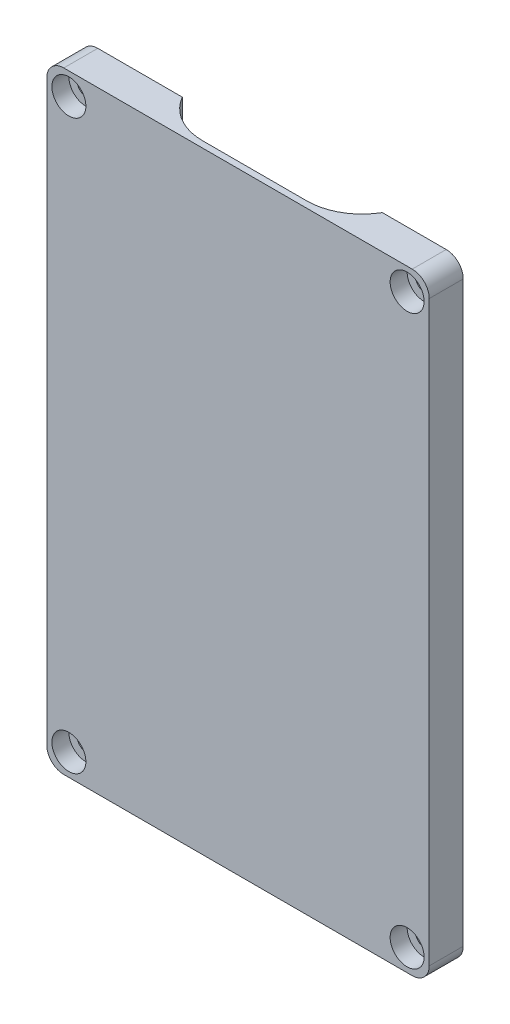
SolidWorks part; units mm, degrees
other "标注1"
sketch "草图6" plane through (-121.7901, 77.7286, -9) normal (-0.0529, 0.1135, -0.9921) x (-0.9984, 0.0112, 0.0545)
ref_plane "前视基准面" through (0, 0, 0) normal (0, 0, 1) x (1, 0, 0)
ref_plane "上视基准面" through (0, 0, 0) normal (0, 1, 0) x (1, 0, 0)
ref_plane "右视基准面" through (0, 0, 0) normal (1, 0, 0) x (0, 0, -1)
sketch "草图1" plane through (0, 0, 0) normal (0, 0, 1) x (1, 0, 0)
  line L1 (-97.7901, 77.7286) -> (-120.2901, 77.7286)
  line L2 (-97.7901, 77.7286) -> (-97.7901, 41.7286)
  line L3 (-97.7901, 41.7286) -> (-120.2901, 41.7286)
  line L4 (-120.2901, 77.7286) -> (-120.2901, 41.7286)
  dimension "D1" = 22.5
  dimension "D2" = 36
extrude "凸台-拉伸1" add sketch "草图1" along normal blind 2
sketch "草图9" plane through (0, 0, 2) normal (0, 0, 1) x (1, 0, 0)
  line L1 (-97.7901, 41.7286) -> (-97.7901, 77.7286) construction
  line L5 (-120.2901, 41.7286) -> (-97.7901, 41.7286) construction
  line L6 (-120.2901, 77.7286) -> (-120.2901, 41.7286) construction
  line L7 (-97.7901, 77.7286) -> (-120.2901, 77.7286) construction
  circle A0 centre (-99.0901, 76.4286) radius 1
  circle A1 centre (-99.0901, 43.0286) radius 1
  circle A2 centre (-118.9901, 43.0286) radius 1
  circle A3 centre (-118.9901, 76.4286) radius 1
  dimension "D1" = 1.3
  dimension "D2" = 1.3
  dimension "D4" = 1.3
  dimension "D5" = 1.3
extrude "切除-拉伸3" cut sketch "草图9" against normal blind 1
sketch "草图10" plane through (0, 0, 1) normal (0, 0, 1) x (1, 0, 0)
  circle A0 centre (-118.9901, 43.0286) radius 0.5
  circle A1 centre (-99.0901, 43.0286) radius 0.5
  circle A2 centre (-99.0901, 76.4286) radius 0.5
  circle A3 centre (-118.9901, 76.4286) radius 0.5
  circle A5 centre (-118.9901, 76.4286) radius 1 construction
  circle A6 centre (-99.0901, 76.4286) radius 1 construction
  circle A7 centre (-118.9901, 43.0286) radius 1 construction
  circle A8 centre (-99.0901, 43.0286) radius 1 construction
  dimension "D1" = 1
extrude "切除-拉伸4" cut sketch "草图10" against normal up to next
fillet "圆角1" radius 1 4 edges at (-97.7901, 77.7286, 1) (-97.7901, 41.7286, 1) (-120.2901, 41.7286, 1) (-120.2901, 77.7286, 1)
sketch "草图11" plane through (0, 0, 0) normal (0, 0, -1) x (-1, 0, 0)
  line L0 (98.7901, 77.7286) -> (119.2901, 77.7286) construction
  line L1 (105.3271, 67.0786) -> (111.0901, 67.0786)
  line L2 (105.3271, 67.0786) -> (105.3271, 64.4229)
  line L3 (105.3271, 64.4229) -> (111.0901, 64.4229)
  line L4 (111.0901, 67.0786) -> (111.0901, 64.4229)
  line L5 (97.7901, 42.7286) -> (97.7901, 76.7286) construction
  dimension "D1" = 10.65
  dimension "D2" = 13.3
extrude "凸台-拉伸2" add sketch "草图11" along normal blind 3
sketch "草图12" plane through (0, 0, 0) normal (0, 0, -1) x (-1, 0, 0)
  line L1 (106.6363, 50.5248) -> (114.6363, 50.5248)
  line L2 (106.6363, 50.5248) -> (106.6363, 49.0286)
  line L3 (106.6363, 49.0286) -> (114.6363, 49.0286)
  line L4 (114.6363, 50.5248) -> (114.6363, 49.0286)
  line L5 (98.7901, 77.7286) -> (119.2901, 77.7286) construction
  dimension "D1" = 28.7
  dimension "D2" = 8
extrude "凸台-拉伸3" add sketch "草图12" along normal blind 2.2
sketch "草图14" plane through (-120.2901, 0, 0) normal (-1, 0, 0) x (0, 0, 1)
  line L1 (0, 75.222) -> (2, 75.222)
  line L2 (0, 75.222) -> (0, 61.7399)
  line L3 (0, 61.7399) -> (2, 61.7399)
  line L4 (2, 75.222) -> (2, 61.7399)
  line L6 (2, 76.7286) -> (2, 42.7286) construction
extrude "切除-拉伸6" cut sketch "草图14" against normal blind 0.0001
fillet "圆角3" radius 2 1 edges at (-120.29, 68.481, 0)
sketch "草图16" plane through (0, 77.7286, 0) normal (0, 1, 0) x (1, 0, 0)
  line L0 (-111.5023, 1.625) -> (-105.3664, 1.625) construction
  line L2 (-111.5023, 4.875) -> (-105.3664, 4.875)
  line L3 (-111.5023, -1.625) -> (-105.3664, -1.625)
  line L4 (-106.2951, 4.875) -> (-112.4951, 4.875) construction
  arc A0 (-111.5023, 4.875) -> (-111.5023, -1.625) centre (-111.5023, 1.625) ccw
  arc A1 (-105.3664, -1.625) -> (-105.3664, 4.875) centre (-105.3664, 1.625) ccw
  arc A4 (-103.4805, 0) -> (-106.2951, 4.875) centre (-106.2951, 1.625) ccw construction
  arc A5 (-112.4951, 4.875) -> (-115.3097, 0) centre (-112.4951, 1.625) ccw construction
  point P4 (-108.4344, 1.625)
extrude "切除-拉伸7" cut sketch "草图16" against normal blind 3.7
fillet "圆角7" radius 1 2 edges at (-120.2901, 61.7399, 1) (-120.2901, 75.222, 1)
